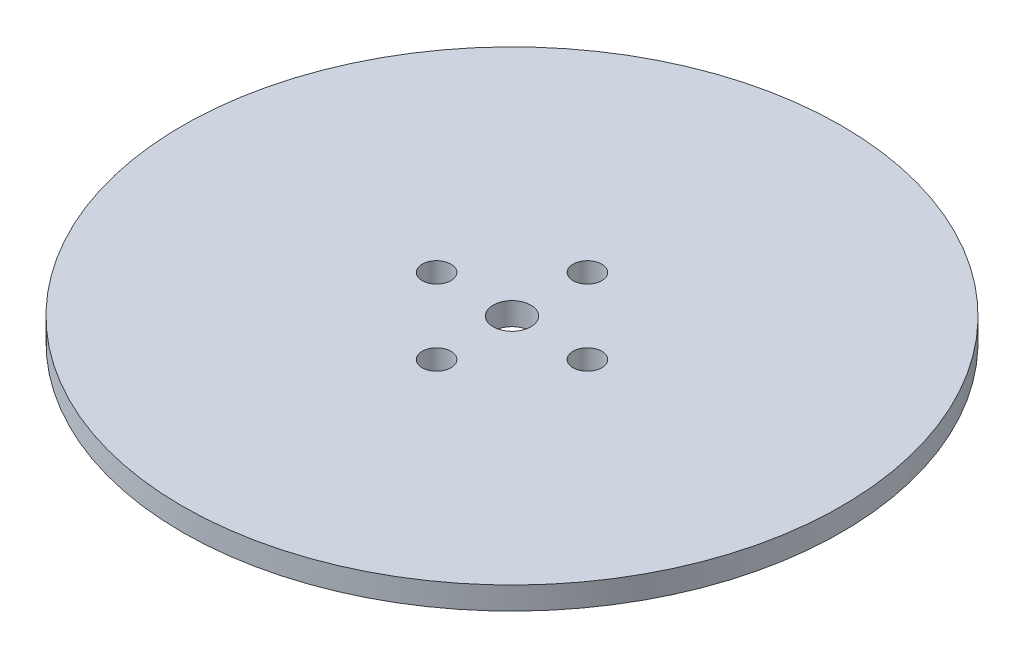
SolidWorks part; units mm, degrees
ref_plane "Front Plane" through (0, 0, 0) normal (0, 0, 1) x (1, 0, 0)
ref_plane "Top Plane" through (0, 0, 0) normal (0, 1, 0) x (1, 0, 0)
ref_plane "Right Plane" through (0, 0, 0) normal (1, 0, 0) x (0, 0, -1)
sketch "Sketch1" plane through (0, 0, 0) normal (0, 1, 0) x (1, 0, 0)
  circle A0 centre (0, 0) radius 87.5
  dimension "FLANGE_OD" = 175
extrude "Boss-Extrude1" add sketch "Sketch1" along normal blind 6
sketch "Sketch2" plane through (0, 0, 0) normal (0, 1, 0) x (1, 0, 0)
  circle A0 centre (0, 0) radius 5
  dimension "BORE_D" = 10
extrude "Cut-Extrude1" cut sketch "Sketch2" along normal through all
sketch "Sketch3" plane through (0, 6, 0) normal (0, 1, 0) x (1, 0, 0)
  circle A0 centre (0, 0) radius 20.0292 construction
  circle A1 centre (-20.0292, 0) radius 3.814
  dimension "BOLT_D" = 7.6281
  dimension "BOLT_PCD" = 40.0585
extrude "Cut-Extrude2" cut sketch "Sketch3" against normal blind 5.6781
pattern_circular "CirPattern1" count 4 over 360 about axis through (0, 0, 0) along (0, 1, 0) of "Cut-Extrude2"
